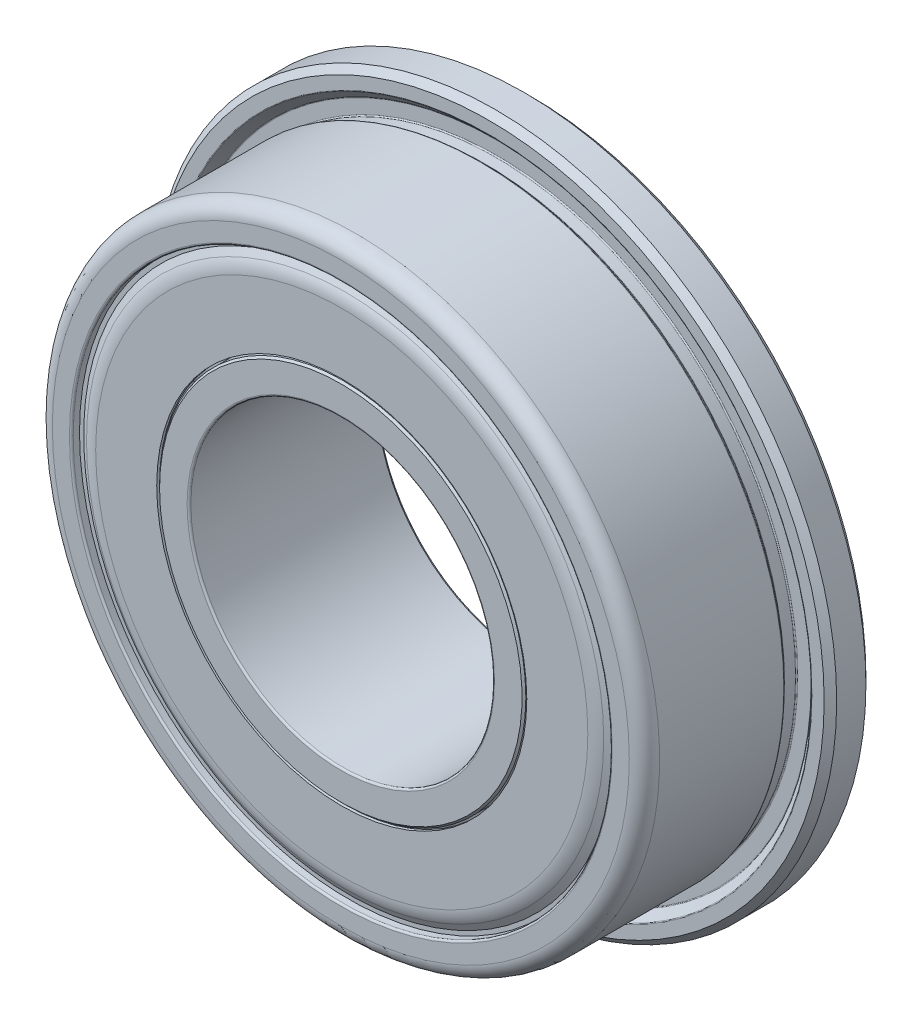
SolidWorks part; units mm, degrees
note: '?' marks a value the reader was unsure of.
ref_plane "Front Plane" through (0, 0, 0) normal (0, 0, 1) x (1, 0, 0)
ref_plane "Top Plane" through (0, 0, 0) normal (0, 1, 0) x (1, 0, 0)
ref_plane "Right Plane" through (0, 0, 0) normal (1, 0, 0) x (0, 0, -1)
sketch "Sketch1" plane through (0, 0, 0) normal (1, 0, 0) x (0, 0, -1)
  line L0 (-2.5, 0) -> (2.5, 0) construction
  line L1 (0, 8) -> (0, -8) construction
  line L2 (2.5, 8) -> (-2.5, 8)
  line L4 (-2.5, 8) -> (-2.5, 7.1)
  line L5 (-2.5, 7.1) -> (-0.7089, 7.1)
  line L6 (2.5, 7.1) -> (0.7089, 7.1)
  line L7 (2.5, 8) -> (2.5, 7.1)
  line L9 (0, 8) -> (0, 6) construction
  line L10 (0, 6) -> (0, 4) construction
  line L11 (-2.5, -7.1) -> (-2.5, 7.1) construction
  line L12 (1.4, -9) -> (2.5, -9)
  line L13 (1.4, -9) -> (1.4, 9)
  line L14 (1.4, 9) -> (2.5, 9)
  line L15 (2.5, -9) -> (2.5, 9)
  line L16 (1.4, -9) -> (2.5, 9) construction
  line L17 (1.4, 9) -> (2.5, -9) construction
  line L18 (-2.5, -4.825) -> (-2.5, 4.825)
  line L24 (0, -8) -> (-2.5, -8)
  line L25 (0, 4) -> (0, 8) construction
  line L26 (-2.5, 4.825) -> (-2.5, 4)
  line L27 (-2.5, 4) -> (2.5, 4)
  line L28 (2.5, 4) -> (2.5, 4.825)
  line L29 (2.5, 4.825) -> (0.5089, 4.825)
  line L30 (-2.5, 4.825) -> (-0.5089, 4.825)
  line L31 (-0.7089, 7.1) -> (-0.7089, 6.645)
  line L32 (-0.7089, 6.645) -> (-0.5089, 6.645)
  line L33 (0.7089, 7.1) -> (0.7089, 6.645)
  line L34 (0.7089, 6.645) -> (0.5089, 6.645)
  arc A3 (-0.5089, 4.825) -> (0.5089, 4.825) centre (0, 6) ccw
  circle A5 centre (0, 5.7495) radius 1
  arc A6 (-0.5089, 6.645) -> (0.5089, 6.645) centre (0, 5.7495) cw
  point P7 (-2.5, 7.1)
  point P13 (-2.4, 7.1)
  point P14 (0, 4)
  point P15 (1.95, 0)
  point P22 (2.5, 0)
  point P25 (-2.5, 0)
  point P27 (-2.5, 0)
  point P28 (-2.3, 7.1)
  point P29 (-2.2, 7.1)
  point P30 (-2.1, 7.1)
  point P31 (-2, 7.1)
  point P32 (-1.9, 7.1)
  point P33 (-1.8, 7.1)
  point P34 (-1.7, 7.1)
  point P37 (-1.6, 7.1)
  point P46 (0, 6.7795)
  point P50 (0, 4.7195)
  point P51 (0, 4.7495)
  point P52 (0, 6.7495)
  dimension "D3" = 2
  dimension "Shaft Dia" = 8
  dimension "Flange Thickness" = 1.1
  dimension "Flange OD" = 18
  dimension "D11" = 14.2
  dimension "D10" = 9.65
  dimension "Width" = 5
  dimension "OD" = 16
  dimension "D4" = 0.03
  dimension "D2" = 0.03
  dimension "D5" = 0.2
  dimension "D6" = 0.1
  dimension "D7" = 1.82
  dimension "D1" = 10
sketch "Sketch2" plane through (0, 0, 0) normal (0, 0, 1) x (1, 0, 0)
  line L0 (0, -4.825) -> (0, 4.825) construction
  circle A0 centre (0, 0) radius 4
  dimension "D1" = 8
sketch "Sketch3" plane through (0, 0, 0) normal (1, 0, 0) x (0, 0, -1)
  line L2 (-2.5, 8) -> (-2.5, 7.1) construction
  line L3 (2.5, 8) -> (-2.5, 8) construction
  line L4 (2.5, 8) -> (2.5, 7.1) construction
  line L5 (2.5, 7.1) -> (0.7089, 7.1) construction
  line L6 (-2.5, 7.1) -> (-0.7089, 7.1) construction
  line L13 (-2.5, 8) -> (-2.5, 7.1)
  line L21 (2.5, 8) -> (-2.5, 8)
  line L22 (2.5, 8) -> (2.5, 7.1)
  line L23 (2.5, 7.1) -> (0.7089, 7.1)
  line L24 (-2.5, 7.1) -> (-0.7089, 7.1)
  line L25 (2.5, 4) -> (-2.5, 4)
  line L27 (-2.5, 4) -> (-2.5, 4.825)
  line L28 (-2.5, 4.825) -> (-0.5089, 4.825)
  line L29 (0.7089, 7.1) -> (0.7089, 6.645) construction
  line L30 (2.5, 4) -> (2.5, 4.825)
  line L31 (2.5, -9) -> (2.5, 9) construction
  line L32 (2.5, 4.825) -> (0.5089, 4.825)
  line L33 (0.7089, 6.645) -> (0.5089, 6.645) construction
  line L34 (-0.7089, 6.645) -> (-0.5089, 6.645) construction
  line L35 (-0.7089, 7.1) -> (-0.7089, 6.645) construction
  line L36 (0.7089, 7.1) -> (0.7089, 6.645)
  line L37 (0.7089, 6.645) -> (0.5089, 6.645)
  line L38 (-0.7089, 6.645) -> (-0.5089, 6.645)
  line L39 (-0.7089, 7.1) -> (-0.7089, 6.645)
  arc A4 (0.5089, 6.645) -> (-0.5089, 6.645) centre (0, 5.7495) ccw construction
  arc A5 (-0.5089, 4.825) -> (0.5089, 4.825) centre (0, 6) ccw construction
  arc A6 (-0.5089, 4.825) -> (0.5089, 4.825) centre (0, 6) ccw
  arc A7 (0.5089, 6.645) -> (-0.5089, 6.645) centre (0, 5.7495) ccw
  point P15 (0, 4)
revolve "Revolve1" add sketch "Sketch3" angle 360 about L0
sketch "Sketch5" plane through (0, 0, 0) normal (1, 0, 0) x (0, 0, -1)
  line L0 (-1, 5.7495) -> (1, 5.7495)
  line L1 (0, 8) -> (0, -8) construction
  circle A0 centre (0, 5.7495) radius 1 construction
  arc A1 (-1, 5.7495) -> (1, 5.7495) centre (0, 5.7495) cw
revolve "Revolve3" add sketch "Sketch5" angle 360 about L0
ref_axis "Axis1" through (0, 0, -2.5) along (0, 0, 1)?
pattern_circular "CirPattern1" count 10 over 360 about axis through (0, 0, 0) along (0, 0, 1) of bodies 122
sketch "Sketch6" plane through (0, 0, 0) normal (1, 0, 0) x (0, 0, -1)
  line L1 (-2.475, 4.825) -> (-2.475, 6.4832)
  line L2 (-2.3866, 6.8132) -> (-2.2845, 6.99)
  line L4 (-2.2845, 6.99) -> (-2.1979, 6.99) construction
  line L5 (-2.2845, 6.99) -> (-2.2845, 7.1)
  line L6 (-2.2845, 7.1) -> (-2.1979, 7.1)
  line L7 (-2.1979, 6.99) -> (-2.4, 6.6399)
  line L8 (-2.4, 6.6399) -> (-2.4, 4.825)
  line L9 (-2.4, 4.825) -> (-2.475, 4.825)
  line L10 (0, 8) -> (0, -8) construction
  line L11 (-2.1979, 7.1) -> (-2.1979, 6.99)
  line L12 (-2.5, 7.1) -> (-0.7089, 7.1) construction
  line L14 (0, 8) -> (0, 6.7795) construction
  arc A0 (-2.475, 6.4832) -> (-2.3866, 6.8132) centre (-1.815, 6.4832) cw
  point P22 (-2.475, 6.66)
  dimension "D8" = 0.66
  dimension "D1" = 30
  dimension "D3" = 0.075
  dimension "D2" = 0.025
  dimension "D4" = 0.075
  dimension "D6" = 0.33
  dimension "D5" = 2.275
  dimension "D7" = 0.11
revolve "Revolve4" add sketch "Sketch6" angle 360 about L0
mirror "Mirror1" about plane through (0, 0, 0) normal (0, 0, 1) of bodies 138
sketch "Sketch9" plane through (0, 0, 2.475) normal (0, 0, 1) x (1, 0, 0)
  circle A2 centre (0, 0) radius 4.875
  circle A3 centre (0, 0) radius 4.875
  dimension "D1" = 0.05
extrude "Cut-Extrude1" cut sketch "Sketch9" against normal through all
sketch "Sketch7" plane through (0, 0, 0) normal (1, 0, 0) x (0, 0, -1)
  line L0 (2.5, 0) -> (-2.5, 0) construction
  line L2 (1.4, 9) -> (2.5, 9)
  line L3 (1.4, 9) -> (1.4, 7.1)
  line L4 (1.4, 7.1) -> (2.5, 7.1)
  line L5 (2.5, 9) -> (2.5, 7.1)
revolve "Revolve5" add sketch "Sketch7" angle 360 about L0
fillet "Fillet2" radius 0.4 1 edges at (8, 0, 2.5)
fillet "Fillet3" radius 0.05 4 edges at (7.1, 0, -2.5) (7.1, 0, 2.5) (7.1, 0, -0.7089) (7.1, 0, 0.7089)
fillet "Fillet6" radius 0.05 4 edges at (4.825, 0, -2.5) (4.825, 0, -0.5089) (4.825, 0, 0.5089) (4.825, 0, 2.5)
sketch "Sketch8" plane through (0, 0, 0) normal (1, 0, 0) x (0, 0, -1)
  line L7 (1.4, 9) -> (1.4, 8) construction
  line L8 (1.4, 8.5) -> (1.62, 8.28)
  line L9 (1.62, 8.28) -> (1.62, 7.89)
  line L10 (1.62, 7.89) -> (1.29, 7.89)
  line L11 (1.29, 7.89) -> (1.18, 8)
  line L12 (1.4, 8) -> (-2.1, 8) construction
  line L13 (1.18, 8) -> (1.4, 8)
  line L14 (1.4, 8) -> (1.4, 8.5)
  dimension "D1" = 45
  dimension "D2" = 45
  dimension "D3" = 0.22
  dimension "D4" = 0.11
  dimension "D5" = 0.11
revolve "Cut-Revolve1" cut sketch "Sketch8" angle 360 about L0
fillet "Fillet5" radius 0.03 5 edges at (8, 0, -1.18) (7.89, 0, -1.29) (7.89, 0, -1.62) (8.28, 0, -1.62) (8.5, 0, -1.4)
chamfer "Chamfer1" distance 0.165 angle 45 2 edges at (-9, 0, -1.4) (-9, 0, -2.5)
fillet "Fillet7" radius 0.05 2 edges at (4, 0, 2.5) (4, 0, -2.5)
equation "\"Balls@CirPattern1\"=\"D1@Sketch1\""
equation "\"D3@Sketch8\" = \"Flange Thickness@Sketch1\" * .2"
equation "\"D4@Sketch8\" = \"D3@Sketch8\" * .5"
equation "\"D5@Sketch8\" = \"D3@Sketch8\" * .5"
equation "\"D1@Chamfer1\"=\"Flange Thickness@Sketch1\"*.15"
equation "\"D1@Fillet6\"=\"D1@Fillet3\""
equation "\"D4@Sketch1\"=\"D2@Sketch1\""
equation "\"D7@Sketch1\" =  ( \"D11@Sketch1\" - \"D10@Sketch1\" )  * .40"
equation "\"D3@Sketch6\"=\"D4@Sketch6\""
equation "\"D8@Sketch6\"=\"D6@Sketch6\"*2"
